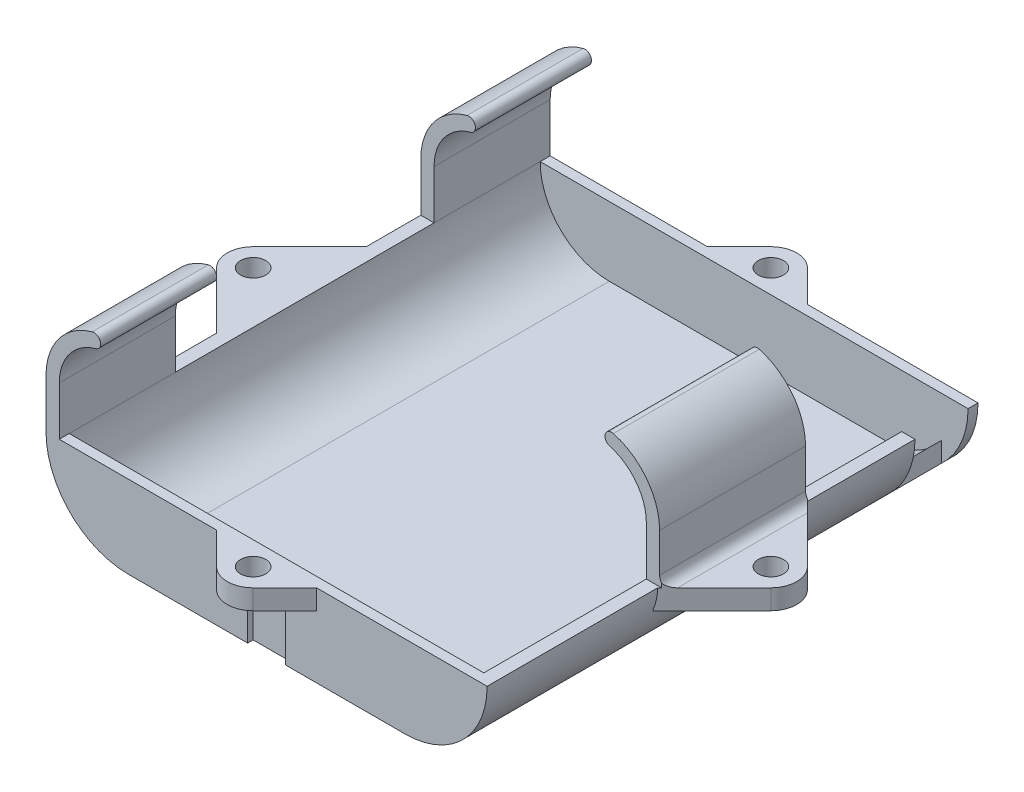
SolidWorks part; units mm, degrees
material "ABS"
ref_plane "Front Plane" through (0, 0, 0) normal (0, 0, 1) x (1, 0, 0)
ref_plane "Top Plane" through (0, 0, 0) normal (0, 1, 0) x (1, 0, 0)
ref_plane "Right Plane" through (0, 0, 0) normal (1, 0, 0) x (0, 0, -1)
sketch "Sketch1" plane through (0, 0, 0) normal (0, 0, 1) x (1, 0, 0)
  line L1 (0, 0) -> (62.5, 0) construction
  line L2 (0, 0) -> (0, 20.8333) construction
  line L3 (0, 20.8333) -> (62.5, 20.8333) construction
  line L4 (62.5, 0) -> (62.5, 20.8333) construction
  circle A0 centre (31.25, 10.4167) radius 10.4167
  circle A1 centre (10.4167, 10.4167) radius 10.4167
  circle A2 centre (52.0833, 10.4167) radius 10.4167
  arc A3 (23.8843, 17.7824) -> (17.7824, 17.7824) centre (20.8333, 20.8333) cw
  arc A4 (38.6157, 17.7824) -> (44.7176, 17.7824) centre (41.6667, 20.8333) ccw
  arc A5 (17.7824, 3.051) -> (23.8843, 3.051) centre (20.8333, 0) cw
  arc A6 (38.6157, 3.051) -> (44.7176, 3.051) centre (41.6667, 0) cw
  point P8 (31.25, 20.8333)
  dimension "D2" = 62.5
extrude "Boss-Extrude1" add sketch "Sketch1" along normal blind 65 contours A1 | A0 A3 A1 | A1 A5 A0 | A0 | A0 A6 A2 | A4 A0 A2 | A2 region at (31.25, 10.4167, 0) region at (41.6667, 5.6133, 0) region at (41.6667, 15.22, 0) region at (52.0833, 10.4167, 0) region at (20.8333, 15.22, 0) region at (20.8333, 5.6133, 0) region at (10.4167, 10.4167, 0)
fillet "Fillet1" radius 2 16 edges at (31.25, 0, 0) (41.6667, 4.3147, 0) (62.5, 10.4167, 0) (41.6667, 16.5186, 0) (31.25, 20.8333, 0) (20.8333, 16.5186, 0) (0, 10.4167, 0) (20.8333, 4.3147, 0) (0, 10.4167, 65) (20.8333, 16.5186, 65) (31.25, 20.8333, 65) (41.6667, 16.5186, 65) (62.5, 10.4167, 65) (41.6667, 4.3147, 65) (31.25, 0, 65) (20.8333, 4.3147, 65)
sketch "Sketch2" plane through (0, 0, 0) normal (0, 0, -1) x (-1, 0, 0)
  line L3 (-52.0833, 0) -> (-10.4167, 0)
  line L4 (-52.0833, -2) -> (-10.4167, -2)
  line L5 (-62.5, 10.4167) -> (-64.5, 10.4167)
  line L6 (0, 10.4167) -> (2, 10.4167)
  arc A0 (-44.7176, 17.7824) -> (-44.7176, 3.051) centre (-52.0833, 10.4167) ccw construction
  arc A1 (-17.7824, 3.051) -> (-17.7824, 17.7824) centre (-10.4167, 10.4167) ccw construction
  arc A5 (-62.5, 10.4167) -> (-52.0833, 0) centre (-52.0833, 10.4167) ccw
  arc A9 (-10.4167, 0) -> (0, 10.4167) centre (-10.4167, 10.4167) ccw
  arc A15 (-64.5, 10.4167) -> (-52.0833, -2) centre (-52.0833, 10.4167) ccw
  arc A16 (-10.4167, -2) -> (2, 10.4167) centre (-10.4167, 10.4167) ccw
  dimension "D1" = 2
extrude "Boss-Extrude2" add sketch "Sketch2" against normal blind 74 separate body
sketch "Sketch3" plane through (0, 10.4167, 0) normal (0, 1, 0) x (1, 0, 0)
  line L0 (64.5, -74) -> (64.5, 0) construction
  line L1 (-2, 0) -> (64.5, 0)
  line L2 (-2, 0) -> (-2, -1.5)
  line L3 (-2, -1.5) -> (64.5, -1.5)
  line L4 (64.5, 0) -> (64.5, -1.5)
  line L6 (-2, -74) -> (64.5, -74)
  line L7 (-2, -74) -> (-2, -72.5)
  line L8 (-2, -72.5) -> (64.5, -72.5)
  line L9 (64.5, -74) -> (64.5, -72.5)
  dimension "D1" = 1.5
  dimension "D2" = 1.5
extrude "Boss-Extrude3" add sketch "Sketch3" against normal up to next
sketch "Sketch4" plane through (0, 10.4167, 0) normal (0, 1, 0) x (1, 0, 0)
  line L0 (31.25, 0) -> (31.25, -74) construction
  line L1 (-2, 0) -> (64.5, 0) construction
  line L2 (-2, -74) -> (64.5, -74) construction
  line L3 (-2, -37) -> (64.5, -37) construction
  line L4 (-2, -74) -> (-2, 0) construction
  line L5 (64.5, -74) -> (64.5, 0) construction
  line L6 (28.4923, 4.7777) -> (22.2146, -1.5)
  line L7 (0, -1.5) -> (62.5, -1.5) construction
  line L8 (22.2146, -1.5) -> (40.2854, -1.5)
  line L9 (52.0833, -1.5) -> (10.4167, -1.5) construction
  line L10 (40.2854, -1.5) -> (34.0077, 4.7777)
  line L11 (73.0277, -34.2423) -> (62.5, -23.7146)
  line L12 (62.5, -72.5) -> (62.5, -1.5) construction
  line L13 (62.5, -23.7146) -> (62.5, -50.2854)
  line L14 (62.5, -50.2854) -> (73.0277, -39.7577)
  line L15 (0, -23.7146) -> (0, -50.2854)
  line L16 (-10.5277, -34.2423) -> (0, -23.7146)
  line L17 (0, -50.2854) -> (-10.5277, -39.7577)
  line L18 (22.2146, -72.5) -> (40.2854, -72.5)
  line L19 (28.4923, -78.7777) -> (22.2146, -72.5)
  line L20 (40.2854, -72.5) -> (34.0077, -78.7777)
  circle A0 centre (31.25, 2.02) radius 1.9
  arc A1 (28.4923, 4.7777) -> (34.0077, 4.7777) centre (31.25, 2.02) cw
  circle A2 centre (70.27, -37) radius 1.9
  arc A3 (73.0277, -34.2423) -> (73.0277, -39.7577) centre (70.27, -37) cw
  circle A4 centre (-7.77, -37) radius 1.9
  arc A5 (-10.5277, -34.2423) -> (-10.5277, -39.7577) centre (-7.77, -37) ccw
  circle A6 centre (31.25, -76.02) radius 1.9
  arc A7 (28.4923, -78.7777) -> (34.0077, -78.7777) centre (31.25, -76.02) ccw
  point P14 (35.15, -1.5)
  point P43 (35.15, -1.5)
  point P44 (0, 0)
  point P45 (0, 0)
  point P46 (26.2937, -1.5)
  point P47 (36.7546, -1.5)
  point P48 (37.9353, -1.5)
  point P49 (0, 0)
  point P50 (0, 0)
  point P51 (62.5, -28.775)
  dimension "D1" = 3.8
  dimension "D3" = 2
  dimension "D4" = 3.8
  dimension "D5" = 2
  dimension "D2" = 2.02
  dimension "D6" = 5.77
  dimension "D7" = 45
  dimension "D8" = 45
extrude "Boss-Extrude4" add sketch "Sketch4" against normal blind 3
sketch "Sketch5" plane through (0, 10.4167, 0) normal (0, 1, 0) x (1, 0, 0)
  line L0 (64.5, -25.7146) -> (64.5, 0) construction
  line L1 (64.5, -1.5) -> (60.5, -1.5)
  line L2 (64.5, -1.5) -> (64.5, -9.5)
  line L3 (64.5, -9.5) -> (60.5, -9.5)
  line L4 (60.5, -1.5) -> (60.5, -9.5)
  line L5 (52.0833, -1.5) -> (62.5, -1.5) construction
  dimension "D1" = 8
  dimension "D2" = 4
extrude "Cut-Extrude1" cut sketch "Sketch5" against normal blind 10
sketch "Sketch6" plane through (0, 0, 74) normal (0, 0, 1) x (1, 0, 0)
  line L0 (64.5, 10.4167) -> (62.5, 10.4167)
  line L1 (38.7854, 10.4167) -> (64.5, 10.4167) construction
  line L2 (62.5, 10.4167) -> (62.5, 17.7716)
  line L3 (31.25, 10.4167) -> (31.25, 23.9435) construction
  line L4 (34.0077, 10.4167) -> (28.4923, 10.4167) construction
  line L6 (64.5, 12.4167) -> (64.5, 17.7716)
  line L7 (64.5, 12.4167) -> (64.5, 12.4167) construction
  line L8 (64.5, 10.4167) -> (64.5, 12.4167)
  line L9 (-2, 10.4167) -> (0, 10.4167)
  line L10 (0, 10.4167) -> (0, 17.7716)
  line L11 (-2, 12.4167) -> (-2, 17.7716)
  line L12 (-2, 10.4167) -> (-2, 12.4167)
  arc A0 (62.5, 17.7716) -> (57, 25) centre (55, 17.7716) ccw
  arc A1 (64.5, 17.7716) -> (57.5333, 26.9276) centre (55, 17.7716) ccw
  arc A3 (57, 25) -> (57.5333, 26.9276) centre (57.2667, 25.9638) cw
  arc A4 (0, 17.7716) -> (5.5, 25) centre (7.5, 17.7716) cw
  arc A5 (5.5, 25) -> (4.9667, 26.9276) centre (5.2333, 25.9638) ccw
  arc A6 (-2, 17.7716) -> (4.9667, 26.9276) centre (7.5, 17.7716) cw
  line M18 (23.7146, 10.4167) -> (-2, 10.4167)
  line M22 (64.5, 10.4167) -> (38.7854, 10.4167)
  dimension "D3" = 7.5
  dimension "D1" = 25
  dimension "D2" = 2
  dimension "D4" = 2
extrude "Boss-Extrude5" add sketch "Sketch6" against normal blind 22 from offset 26 contours A3 A0 L2 L8 L6 A1 M22 region at (63.5, 10.6015, 74) offset against normal yes
extrude "Boss-Extrude6" add sketch "Sketch6<3>" against normal blind 17.5 contours A6 L11 L12 L10 A4 A5 M18 region at (-1.8152, 11.4167, 74)
sketch "Sketch6<3>" plane through (0, 0, 74) normal (0, 0, 1) x (1, 0, 0) same geometry as "Sketch6"
ref_plane "Plane1" through (0, 0, 37) normal (0, 0, 1) x (1, 0, 0)
mirror "Mirror1" about plane through (0, 0, 37) normal (0, 0, 1) of "Boss-Extrude6"
fillet "Fillet2" radius 1.5 1 edges at (64.5, 10.4167, 37)
delete or keep bodies "Body-Delete/Keep 1" type delete bodies bodies 101
sketch "Sketch8" plane through (0, -2, 0) normal (0, -1, 0) x (1, 0, 0)
  line L1 (28.4, 0) -> (34.1, 0)
  line L2 (28.4, 0) -> (28.4, 0.83)
  line L3 (28.4, 0.83) -> (34.1, 0.83)
  line L4 (34.1, 0) -> (34.1, 0.83)
  line L5 (10.4167, 37) -> (52.0833, 37) construction
  line L6 (10.4167, 74) -> (10.4167, 0) construction
  line L7 (52.0833, 74) -> (52.0833, 0) construction
  line L8 (28.4, 73.17) -> (34.1, 73.17)
  line L9 (34.1, 74) -> (34.1, 73.17)
  line L10 (28.4, 74) -> (34.1, 74)
  line L11 (28.4, 74) -> (28.4, 73.17)
  line L13 (52.0833, 0) -> (10.4167, 0) construction
  circle A0 centre (31.25, -2.02) radius 1.9 construction
  point P20 (31.25, 0)
  dimension "D1" = 2.85
  dimension "D2" = 5.7
extrude "Cut-Extrude4" cut sketch "Sketch8" against normal up to surface (9.4167 mm away) up to face at (29.35, 7.4167, -2.02)
